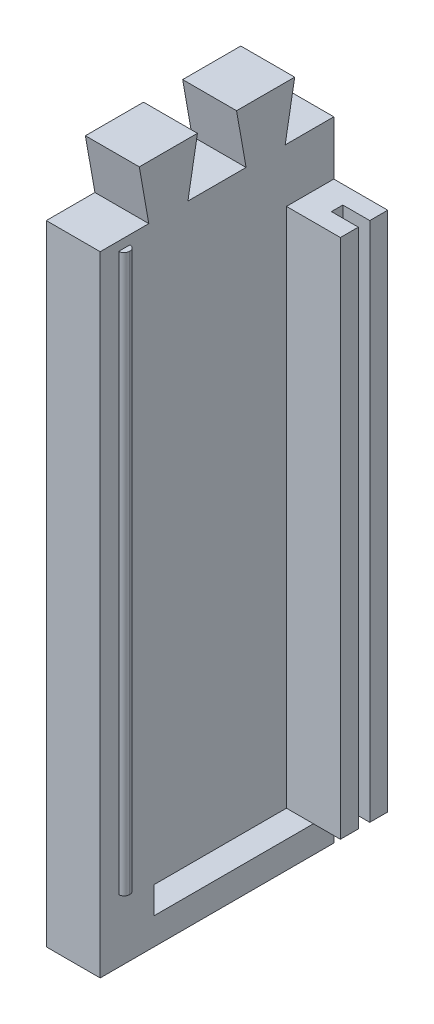
SolidWorks part; units mm, degrees
note: The reader was unsure of these and kept them because the rebuilt part matched: shared geometry of "Sketch1<3>", "Sketch1<5>", "Sketch1<7>".
ref_plane "Front Plane" through (0, 0, 0) normal (0, 0, 1) x (1, 0, 0)
ref_plane "Top Plane" through (0, 0, 0) normal (0, 1, 0) x (1, 0, 0)
ref_plane "Right Plane" through (0, 0, 0) normal (1, 0, 0) x (0, 0, -1)
sketch "Sketch1" plane through (0, 0, 0) normal (1, 0, 0) x (0, 0, -1)
  line L0 (-65, 160) -> (-37.942, 160)
  line L1 (-65, -190) -> (65, -190)
  line L2 (-65, -190) -> (-65, 190)
  line L3 (-65, 190) -> (-43.232, 190)
  line L4 (65, -190) -> (65, 190)
  line L5 (-65, -190) -> (65, 190) construction
  line L6 (-65, 190) -> (65, -190) construction
  line L7 (-65, 0) -> (65, 0) construction
  line L8 (-65, -160) -> (65, -160)
  line L9 (-37.942, 160) -> (-16.174, 160)
  line L10 (-16.174, 160) -> (16.174, 160)
  line L11 (16.174, 160) -> (37.942, 160)
  line L12 (37.942, 160) -> (65, 160)
  line L13 (-43.232, 190) -> (-10.884, 190)
  line L14 (-10.884, 190) -> (10.884, 190)
  line L15 (10.884, 190) -> (43.232, 190)
  line L16 (43.232, 190) -> (65, 190)
  line L17 (-37.942, 160) -> (-43.232, 190)
  line L18 (-10.884, 190) -> (-16.174, 160)
  line L19 (10.884, 190) -> (16.174, 160)
  line L20 (43.232, 190) -> (37.942, 160)
  line L21 (65, 130) -> (38.65, 130)
  line L22 (65, -160) -> (-35, -160)
  line L23 (65, -160) -> (65, -175)
  line L24 (65, -175) -> (-35, -175)
  line L25 (-35, -160) -> (-35, -175)
  line L26 (-54.66, 155) -> (-48.46, 155)
  line L27 (-54.66, 155) -> (-54.66, -155)
  line L28 (-54.66, -155) -> (-48.46, -155)
  line L29 (-48.46, 155) -> (-48.46, -155)
  line L30 (-54.66, 155) -> (-48.46, -155) construction
  line L31 (-54.66, -155) -> (-48.46, 155) construction
  line L32 (38.65, -160) -> (65, -160)
  line L33 (38.65, -160) -> (38.65, 160)
  line L34 (38.65, 160) -> (65, 160)
  line L35 (65, -160) -> (65, 160)
  point P0 (0, 0)
  point P12 (-51.56, 0)
  dimension "D1" = 380
  dimension "D2" = 130
  dimension "D3" = 30
  dimension "D4" = 21.768
  dimension "D5" = 32.348
  dimension "D6" = 27.058
  dimension "D7" = 10.34
  dimension "D8" = 6.2
  dimension "D9" = 310
  dimension "D10" = 30
  dimension "D11" = 15
  dimension "D12" = 100
  dimension "D13" = 26.35
  dimension "D14" = 30
extrude "Boss-Extrude2" add sketch "Sketch1" against normal blind 30
extrude "Boss-Extrude3" add sketch "Sketch1<3>" along normal blind 3 separate body contours L29 L26 L27 L28
sketch "Sketch1<3>" plane through (0, 0, 0) normal (1, 0, 0) x (0, 0, -1) same geometry as "Sketch1"
fillet "Fillet2" radius 3 2 edges at (3, 0, 48.46) (3, 0, 54.66)
extrude "Cut-Extrude1" cut sketch "Sketch1<5>" against normal blind 15 contours L8 L25 L24 L4
sketch "Sketch1<5>" plane through (0, 0, 0) normal (1, 0, 0) x (0, 0, -1) same geometry as "Sketch1"
extrude "Boss-Extrude6" add sketch "Sketch1<7>" along normal blind 30 contours L33 L22 L4 L21
sketch "Sketch1<7>" plane through (0, 0, 0) normal (1, 0, 0) x (0, 0, -1) same geometry as "Sketch1"
sketch "Sketch4" plane through (30, 0, 0) normal (1, 0, 0) x (0, 0, -1)
  line L0 (38.65, -160) -> (65, -160) construction
  line L1 (55, -160) -> (48.65, -160)
  line L2 (55, -160) -> (55, 130)
  line L3 (55, 130) -> (48.65, 130)
  line L4 (48.65, -160) -> (48.65, 130)
  line L5 (65, 130) -> (38.65, 130) construction
  line L6 (65, -160) -> (65, 130) construction
  dimension "D1" = 10
  dimension "D2" = 6.35
extrude "Cut-Extrude4" cut sketch "Sketch4" against normal blind 15
